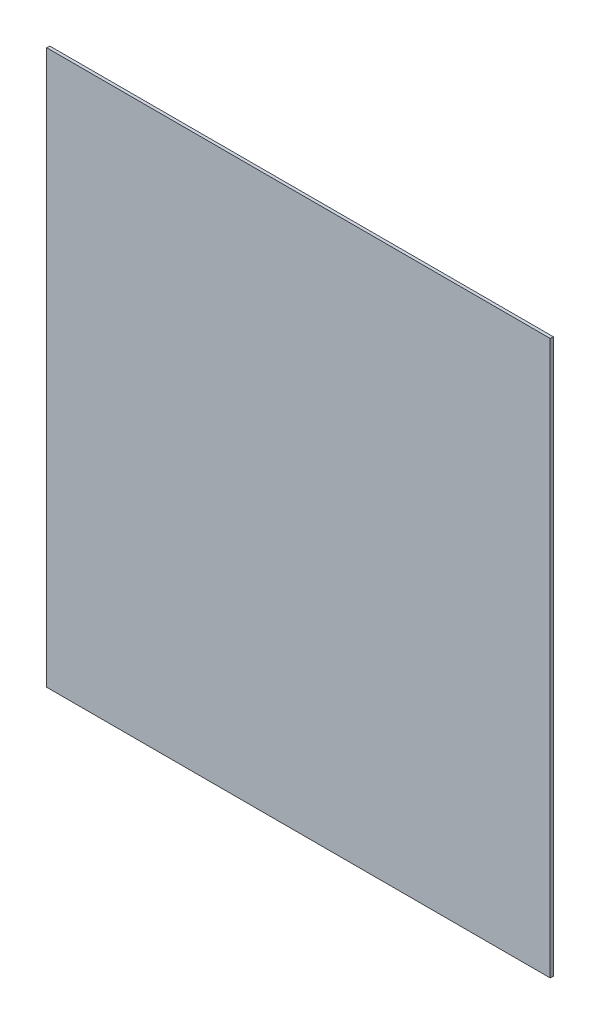
SolidWorks part; units mm, degrees
material "AISI 316 Annealed Stainless Steel Bar (SS)"
ref_plane "Front Plane" through (0, 0, 0) normal (0, 0, 1) x (1, 0, 0)
ref_plane "Top Plane" through (0, 0, 0) normal (0, 1, 0) x (1, 0, 0)
ref_plane "Right Plane" through (0, 0, 0) normal (1, 0, 0) x (0, 0, -1)
sketch "Sketch1" plane through (0, 0, 0) normal (0, 0, 1) x (1, 0, 0)
  line L1 (250, -275) -> (-250, -275)
  line L2 (250, -275) -> (250, 275)
  line L3 (250, 275) -> (-250, 275)
  line L4 (-250, -275) -> (-250, 275)
  line L5 (250, -275) -> (-250, 275) construction
  line L6 (250, 275) -> (-250, -275) construction
  point P0 (0, 0)
  dimension "D1" = 500
  dimension "D2" = 550
extrude "Boss-Extrude1" add sketch "Sketch1" along normal mid plane 3
